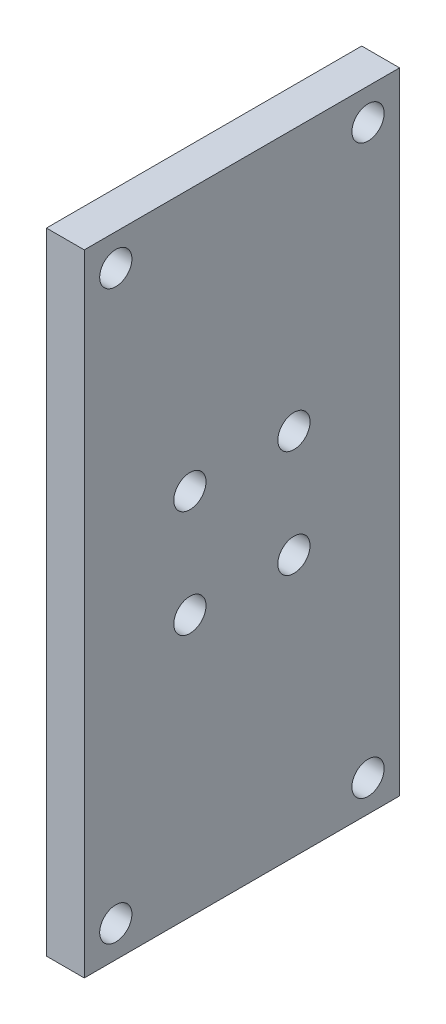
SolidWorks part; units mm, degrees
ref_plane "Front Plane" through (0, 0, 0) normal (1, 0, 0) x (0, 1, 0)
ref_plane "Top Plane" through (0, 0, 0) normal (0, 0, 1) x (0, 1, 0)
ref_plane "Right Plane" through (0, 0, 0) normal (0, 1, 0) x (-1, 0, 0)
sketch "Sketch1" plane through (0, 0, 0) normal (1, 0, 0) x (0, 1, 0)
  line L0 (0, 25) -> (0, -25) construction
  line L1 (-50, -25) -> (50, -25)
  line L2 (-50, -25) -> (-50, 25)
  line L3 (-50, 25) -> (50, 25)
  line L4 (50, -25) -> (50, 25)
  line L5 (-50, -25) -> (50, 25) construction
  line L6 (-50, 25) -> (50, -25) construction
  line L8 (-8.5, -8.25) -> (8.5, -8.25) construction
  line L9 (-8.5, -8.25) -> (-8.5, 8.25) construction
  line L10 (-8.5, 8.25) -> (8.5, 8.25) construction
  line L11 (8.5, -8.25) -> (8.5, 8.25) construction
  line L12 (-8.5, -8.25) -> (8.5, 8.25) construction
  line L13 (-8.5, 8.25) -> (8.5, -8.25) construction
  line L14 (-45, -20) -> (45, -20) construction
  line L15 (-45, -20) -> (-45, 20) construction
  line L16 (-45, 20) -> (45, 20) construction
  line L17 (45, -20) -> (45, 20) construction
  line L18 (-45, -20) -> (45, 20) construction
  line L19 (-45, 20) -> (45, -20) construction
  circle A0 centre (-8.5, 8.25) radius 2.555
  circle A1 centre (-8.5, -8.25) radius 2.555
  circle A2 centre (8.5, -8.25) radius 2.555
  circle A3 centre (8.5, 8.25) radius 2.555
  circle A4 centre (-45, 20) radius 2.555
  circle A5 centre (-45, -20) radius 2.555
  circle A6 centre (45, 20) radius 2.555
  circle A7 centre (45, -20) radius 2.555
  point P0 (0, 0)
  point P8 (0, 0)
  point P17 (0, 0)
  dimension "D5" = 5.11
  dimension "D6" = 5.11
  dimension "D9" = 5.11
  dimension "D10" = 5.11
  dimension "D1" = 16.5
  dimension "D2" = 17
  dimension "D3" = 100
  dimension "D4" = 50
  dimension "D7" = 5
  dimension "D8" = 5
extrude "Boss-Extrude1" add sketch "Sketch1" along normal blind 6
